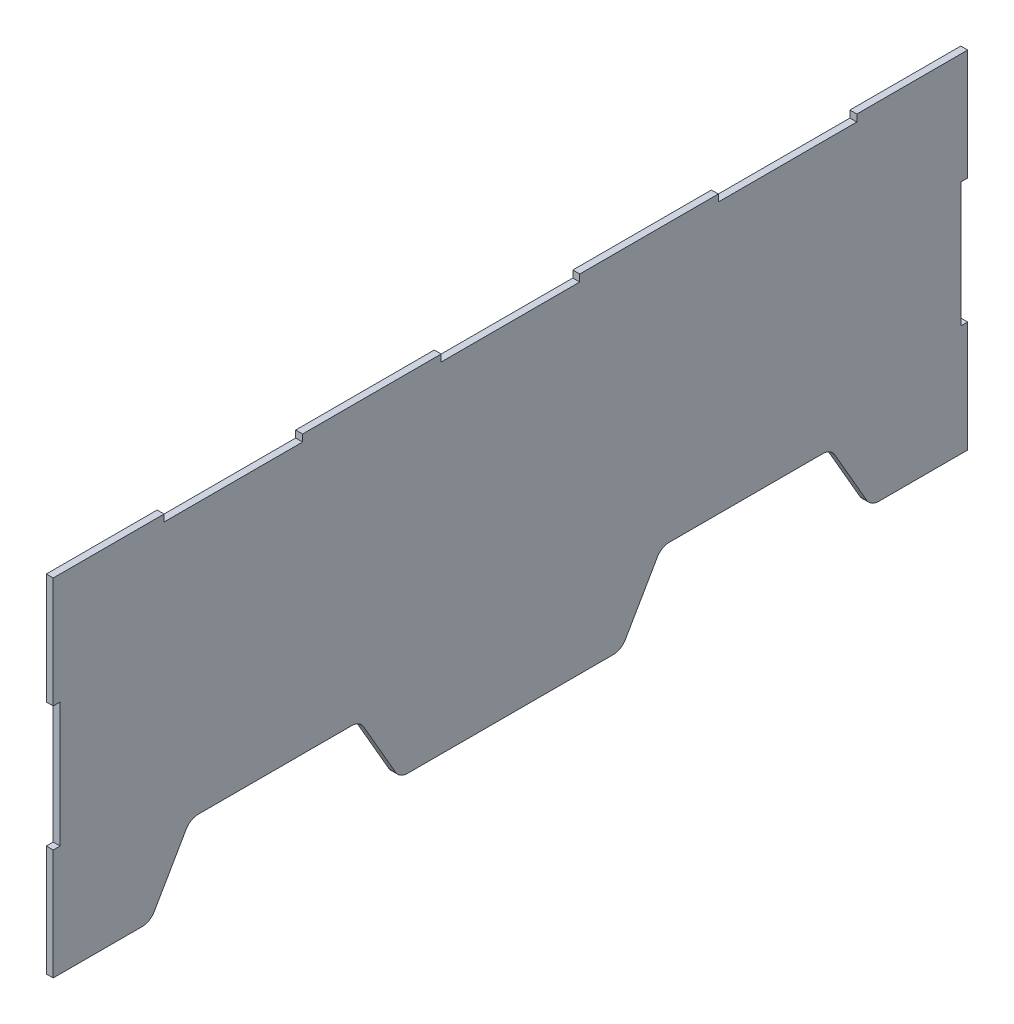
SolidWorks part; units mm, degrees
ref_plane "Ebene vorne" through (0, 0, 0) normal (0, 0, 1) x (1, 0, 0)
ref_plane "Ebene oben" through (0, 0, 0) normal (0, 1, 0) x (1, 0, 0)
ref_plane "Ebene rechts" through (0, 0, 0) normal (1, 0, 0) x (0, 0, -1)
sketch "Skizze1" plane through (0, 0, 0) normal (1, 0, 0) x (0, 0, -1)
  line L1 (-325, 125) -> (325, 125)
  line L2 (-325, 125) -> (-325, -125)
  line L3 (-325, -125) -> (325, -125)
  line L4 (325, 125) -> (325, -125)
  line L5 (-325, 125) -> (325, -125) construction
  line L6 (-325, -125) -> (325, 125) construction
  point P0 (0, 0)
  dimension "D1" = 650
  dimension "D2" = 250
extrude "Aufsatz-Linear austragen1" add sketch "Skizze1" along normal blind 5
sketch "Skizze2" plane through (5, 0, 0) normal (1, 0, 0) x (0, 0, -1)
  line L0 (0, -125) -> (0, 125) construction
  line L1 (-325, 125) -> (-330, 125)
  line L2 (-325, 125) -> (-325, 45)
  line L3 (-325, 45) -> (-330, 45)
  line L4 (-330, 125) -> (-330, 45)
  line L5 (-325, -125) -> (-330, -125)
  line L6 (-325, -125) -> (-325, -45)
  line L7 (-325, -45) -> (-330, -45)
  line L8 (-330, -125) -> (-330, -45)
  line L9 (-325, -125) -> (325, -125) construction
  line L10 (325, 125) -> (-325, 125) construction
  line L11 (330, -125) -> (330, -45)
  line L12 (325, -45) -> (330, -45)
  line L13 (325, -125) -> (325, -45)
  line L14 (325, -125) -> (330, -125)
  line L15 (330, 125) -> (330, 45)
  line L16 (325, 45) -> (330, 45)
  line L17 (325, 125) -> (325, 45)
  line L18 (325, 125) -> (330, 125)
  dimension "D1" = 5
  dimension "80" = 80
extrude "Aufsatz-Linear austragen2" add sketch "Skizze2" against normal up to surface (5 mm away) up to face at (0, 0, 0)
sketch "Skizze3" plane through (5, 0, 0) normal (1, 0, 0) x (0, 0, -1)
  line L0 (0, 125) -> (0, -125) construction
  line L2 (-330, -125) -> (330, -125) construction
  line L15 (-325, 0) -> (325, 0) construction
  line L16 (-325, 45) -> (-325, -45) construction
  line L17 (325, -45) -> (325, 45) construction
  line L18 (150, 120) -> (250, 120)
  line L19 (150, 120) -> (150, 125)
  line L20 (150, 125) -> (250, 125)
  line L21 (-250, 120) -> (-250, 125)
  line L22 (-150, 125) -> (-250, 125)
  line L23 (-150, 120) -> (-150, 125)
  line L24 (-150, 120) -> (-250, 120)
  line L25 (250, 120) -> (250, 125)
  line L26 (50, 120) -> (50, 125)
  line L27 (-50, 125) -> (50, 125)
  line L28 (-50, 120) -> (-50, 125)
  line L29 (50, 120) -> (-50, 120)
  line L30 (330, 125) -> (-330, 125) construction
  line L31 (0, 125) -> (0, 120) construction
  point P6 (0, 140)
  point P37 (1.9829, 132.6182)
  dimension "D1" = 100
  dimension "D2" = 100
  dimension "D3" = 5
  dimension "D4" = 100
extrude "Schnitt-Linear austragen1" cut sketch "Skizze3" against normal through all
sketch "Skizze4" plane through (5, 0, 0) normal (1, 0, 0) x (0, 0, -1)
  line L0 (0, 120) -> (0, -125) construction
  line L1 (-50, 120) -> (50, 120) construction
  line L2 (-330, -125) -> (330, -125) construction
  line L3 (-260, -125) -> (-231.1325, -75)
  line L4 (-231.1325, -75) -> (-108.8675, -75)
  line L5 (-108.8675, -75) -> (-80, -125)
  line L6 (-80, -125) -> (-260, -125)
  line L7 (-170, -125) -> (-170, -75) construction
  line L8 (170, -125) -> (170, -75) construction
  line L9 (80, -125) -> (260, -125)
  line L10 (108.8675, -75) -> (80, -125)
  line L11 (231.1325, -75) -> (108.8675, -75)
  line L12 (260, -125) -> (231.1325, -75)
  dimension "D1" = 60
  dimension "D2" = 60
  dimension "D3" = 50
  dimension "D4" = 180
  dimension "D5" = 160
extrude "Schnitt-Linear austragen2" cut sketch "Skizze4" against normal blind 10
fillet "Verrundung1" radius 10 8 edges at (2.5, -75, -231.1325) (2.5, -125, -260) (2.5, -125, -80) (2.5, -75, -108.8675) (2.5, -125, 80) (2.5, -75, 108.8675) (2.5, -75, 231.1325) (2.5, -125, 260)
